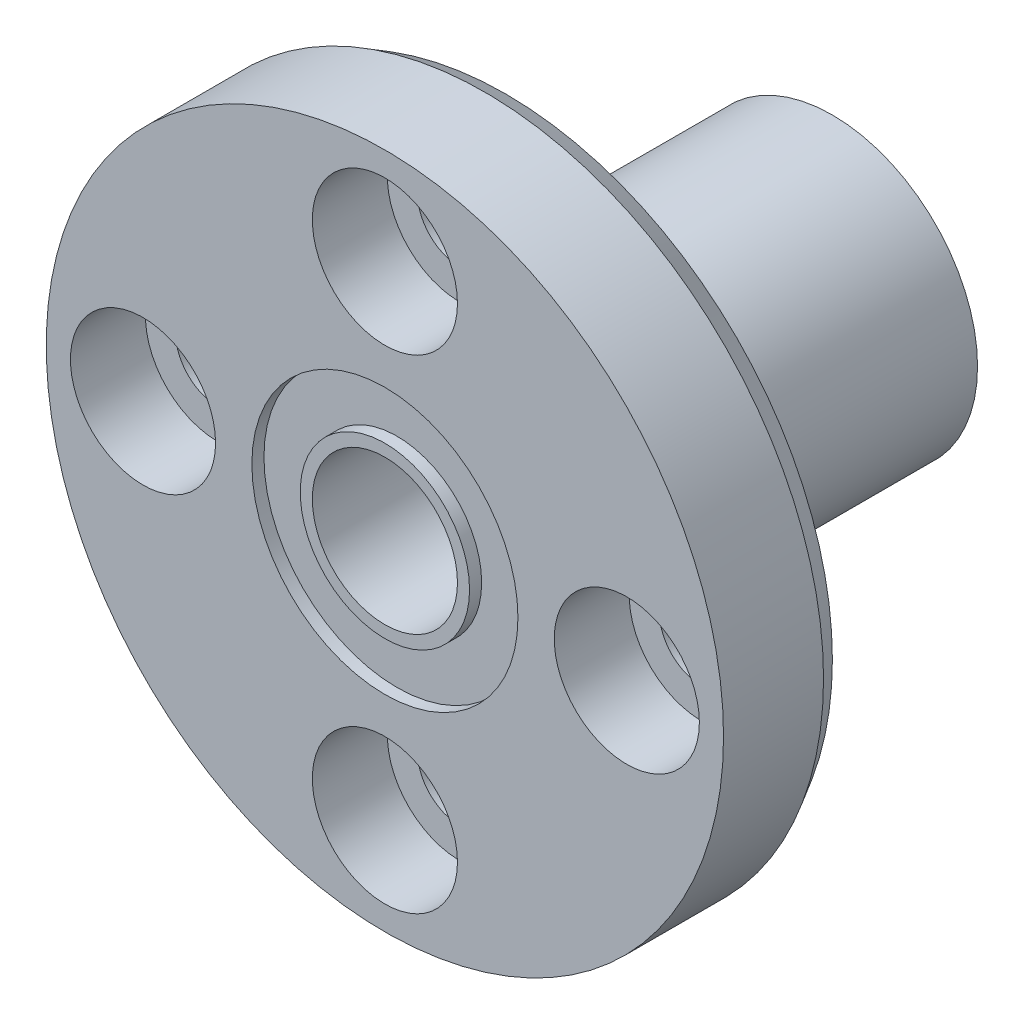
SolidWorks part; units mm, degrees
ref_plane "Front Plane" through (0, 0, 0) normal (0, 0, 1) x (1, 0, 0)
ref_plane "Top Plane" through (0, 0, 0) normal (0, 1, 0) x (1, 0, 0)
ref_plane "Right Plane" through (0, 0, 0) normal (1, 0, 0) x (0, 0, -1)
sketch "Sketch1" plane through (0, 0, 0) normal (0, 0, 1) x (1, 0, 0)
  circle A0 centre (0, 0) radius 14
  circle A1 centre (0, 0) radius 3
  dimension "D1" = 28
  dimension "D2" = 6
extrude "Boss-Extrude1" add sketch "Sketch1" along normal blind 5
sketch "Sketch2" plane through (0, 0, 0) normal (0, 0, -1) x (-1, 0, 0)
  circle A0 centre (0, 0) radius 3
  circle A1 centre (0, 0) radius 3 construction
  circle A2 centre (0, 0) radius 6
  dimension "D1" = 12
extrude "Boss-Extrude2" add sketch "Sketch2" along normal blind 14
sketch "Sketch3" plane through (0, 0, 5) normal (0, 0, 1) x (1, 0, 0)
  line L0 (0, 10) -> (0, -10) construction
  line L1 (-10, 0) -> (10, 0) construction
  circle A0 centre (0, 0) radius 10 construction
  circle A1 centre (-10, 0) radius 1.75
  circle A2 centre (0, -10) radius 1.75
  circle A3 centre (10, 0) radius 1.75
  circle A4 centre (0, 10) radius 1.75
  dimension "D1" = 20
  dimension "D2" = 3.5
extrude "Cut-Extrude1" cut sketch "Sketch3" against normal through all
sketch "Sketch4" plane through (0, 0, 5) normal (0, 0, 1) x (1, 0, 0)
  circle A0 centre (-10, 0) radius 3
  circle A1 centre (0, -10) radius 3
  circle A2 centre (0, -10) radius 1.75 construction
  circle A3 centre (10, 0) radius 3
  circle A4 centre (0, 10) radius 3
  circle A5 centre (0, 10) radius 1.75 construction
  dimension "D1" = 6
extrude "Cut-Extrude2" cut sketch "Sketch4" against normal blind 3.1
sketch "Sketch5" plane through (0, 0, 5) normal (0, 0, 1) x (1, 0, 0)
  circle A0 centre (0, 0) radius 5.5
  circle A1 centre (0, 0) radius 3 construction
  circle A2 centre (0, 0) radius 3.5
  dimension "D1" = 2.5
  dimension "D2" = 0.5
extrude "Cut-Extrude3" cut sketch "Sketch5" against normal blind 0.5
sketch "Sketch6" plane through (0, 0, -14) normal (0, 0, -1) x (-1, 0, 0)
  circle A0 centre (0, 0) radius 3.5
  circle A2 centre (0, 0) radius 3 construction
  circle A3 centre (0, 0) radius 5.5
  circle A4 centre (0, 0) radius 5.5 construction
  dimension "D1" = 0.5
extrude "Cut-Extrude4" cut sketch "Sketch6" against normal blind 0.5
chamfer "Chamfer1" distance 0.5 angle 60 6 edges at (1.75, -10, 0) (11.75, 0, 0) (-8.25, 0, 0) (1.75, 10, 0) (14, 0, 0) (-6, 0, -14) first distance on face at (1.75, -10, 0) first distance on face at (11.75, 0, 0) first distance on face at (-8.25, 0, 0) first distance on face at (1.75, 10, 0) first distance on face at (-6, 0, -14)
chamfer "Chamfer2" distance 0.2 angle 60 1 edges at (-3, 0, -14) first distance on face at (-3, 0, -14)
chamfer "Chamfer3" distance 0.1 angle 60 1 edges at (-3.5, 0, -14) first distance on face at (-3.5, 0, -13.5)
